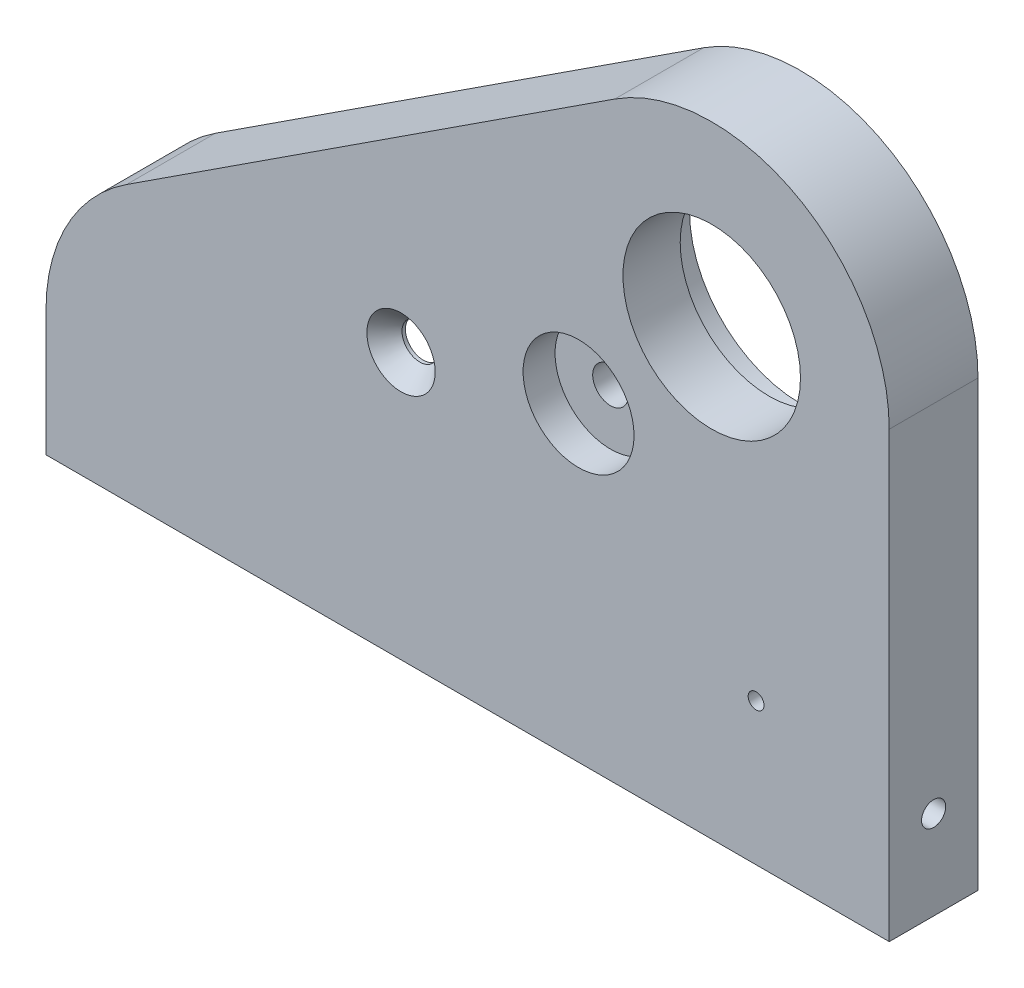
SolidWorks part; units mm, degrees
material "6061 Alloy"
ref_plane "Front Plane" through (0, 0, 0) normal (0, 0, 1) x (1, 0, 0)
ref_plane "Top Plane" through (0, 0, 0) normal (0, 1, 0) x (1, 0, 0)
ref_plane "Right Plane" through (0, 0, 0) normal (1, 0, 0) x (0, 0, -1)
sketch "Sketch1" plane through (0, 0, 0) normal (0, 0, 1) x (1, 0, 0)
  line L0 (25.4, 0) -> (25.4, -63.5)
  line L1 (25.4, -63.5) -> (-95.25, -63.5)
  line L2 (-95.25, -63.5) -> (-95.25, -31.75)
  line L3 (-13.8669, 21.2807) -> (-95.25, -31.75)
  arc A0 (25.4, 0) -> (-13.8669, 21.2807) centre (0, 0) ccw
  dimension "D1" = 50.8
  dimension "D2" = 63.5
  dimension "D4" = 31.75
  dimension "D5" = 120.65
extrude "Boss-Extrude1" add sketch "Sketch1" along normal mid plane 12.7
sketch "Sketch4" plane through (0, 0, 6.35) normal (0, 0, 1) x (1, 0, 0)
  circle A0 centre (0, 0) radius 12.7
  dimension "D1" = 25.4
extrude "Cut-Extrude3" cut sketch "Sketch4" against normal through all
sketch "Sketch5" plane through (0, 0, -6.35) normal (0, 0, -1) x (-1, 0, 0)
  circle A0 centre (0, 0) radius 15.875
  dimension "D1" = 31.75
extrude "Cut-Extrude4" cut sketch "Sketch5" against normal blind 4.5085
fillet "Fillet1" radius 25.4 1 edges at (-95.25, -31.75, 0)
hole_wizard "#8-32 Tapped Hole2" positions "Sketch17" profile "Sketch18" tap size "#8-32" standard "Ansi Inch"
sketch "Sketch17" plane through (25.4, 0, 0) normal (1, 0, 0) x (0, 0, -1)
  line L0 (-6.35, -63.5) -> (6.35, -63.5) construction
  point P0 (0, -50.8)
  dimension "D1" = 12.7
sketch "Sketch18" plane through (25.4, -50.8, 0) normal (0, 1, 0) x (0, 0, -1)
  line L0 (0, 0) -> (0, 11.7058)
  line L1 (0, 11.7058) -> (1.7272, 10.668)
  line L2 (1.7272, 10.668) -> (1.7272, 0)
  line L5 (1.7272, 0) -> (0, 0)
  line L10 (0, 11.7058) -> (-1.7272, 10.668) construction
  line L11 (0, -6.35) -> (0, 107.95) construction
  dimension "Tap Drill Dia." = 3.4544
  dimension "Tap Drill Depth" = 10.668
  dimension "Drill Angle" = 118
hole_wizard "1/4-20 Tapped Hole1" positions "Sketch24" profile "Sketch25" tap size "1/4-20" standard "Ansi Inch" end condition through all
sketch "Sketch24" plane through (0, 0, 6.35) normal (0, 0, 1) x (1, 0, 0)
  point P0 (-19.05, -19.05)
  dimension "D1" = 19.05
  dimension "D2" = 19.05
sketch "Sketch25" plane through (-19.05, -19.05, 6.35) normal (1, 0, 0) x (0, -1, 0)
  line L0 (0, 0) -> (0, 12.7)
  line L1 (0, 12.7) -> (2.5527, 12.7)
  line L2 (2.5527, 12.7) -> (2.5527, 0)
  line L5 (2.5527, 0) -> (0, 0)
  line L11 (0, -6.35) -> (0, 107.95) construction
  dimension "Thread Major Dia." = 5.1054
  dimension "Thru Tap Drill Depth" = 12.7
sketch "Sketch27" plane through (0, 0, 6.35) normal (0, 0, 1) x (1, 0, 0)
  circle A0 centre (-19.05, -19.05) radius 7.9375
  dimension "D1" = 15.875
extrude "Cut-Extrude6" cut sketch "Sketch27" against normal blind 4.572
sketch "Sketch28" plane through (0, 0, -6.35) normal (0, 0, -1) x (-1, 0, 0)
  line L0 (-19.05, -16.8005) -> (-19.05, -57.15)
  line L1 (-19.05, -57.15) -> (88.9, -57.15)
  line L2 (88.9, -57.15) -> (88.9, -45.5155)
  line L3 (80.2502, -29.555) -> (24.4761, 6.7884)
  line L4 (95.25, -63.5) -> (95.25, -45.5155)
  line L5 (83.7169, -24.2348) -> (13.8669, 21.2807)
  line L6 (-25.4, 0) -> (-25.4, -63.5)
  line L7 (-25.4, -63.5) -> (95.25, -63.5)
  line L8 (95.25, -63.5) -> (95.25, -45.5155) construction
  line L9 (83.7169, -24.2348) -> (13.8669, 21.2807) construction
  line L10 (-25.4, 0) -> (-25.4, -63.5) construction
  line L11 (-25.4, -63.5) -> (95.25, -63.5) construction
  circle A0 centre (0, 0) radius 25.4
  arc A1 (88.9, -45.5155) -> (80.2502, -29.555) centre (69.85, -45.5155) ccw
  arc A2 (95.25, -45.5155) -> (83.7169, -24.2348) centre (69.85, -45.5155) ccw
  arc A3 (13.8669, 21.2807) -> (-25.4, 0) centre (0, 0) ccw
  arc A4 (95.25, -45.5155) -> (83.7169, -24.2348) centre (69.85, -45.5155) ccw construction
  arc A5 (13.8669, 21.2807) -> (-25.4, 0) centre (0, 0) ccw construction
  circle A6 centre (19.05, -19.05) radius 9.525
  arc A7 (13.2298, -26.59) -> (5.3888, -24.8218) centre (7.4096, -34.1299) ccw
  arc A8 (28.5743, -19.1637) -> (48.2069, -8.675) centre (41.2734, -19.3154) cw
  dimension "D6" = 19.05
  dimension "D7" = 9.525
  dimension "D8" = 12.7
  dimension "D2" = 6.35
  dimension "D3" = 6.35
  dimension "D4" = 6.35
  dimension "D5" = 6.35
  dimension "D1" = 0
extrude "Cut-Extrude8" cut sketch "Sketch28" against normal offset from surface (9.525 mm away) 3.175 contours A8 A6 A7 A0 L0 L1 L2 A1 L3 region at (-34.7797, -38.1357, -6.35) up to face at (-11.1125, -19.05, 6.35)
fillet "Fillet2" radius 6.35 3 edges at (-88.9, -57.15, -1.5875) (19.05, -57.15, -1.5875) (19.05, -16.8005, -1.5875)
hole_wizard "#8-32 Tapped Hole1" positions "Sketch20" profile "Sketch21" tap size "#8-32" standard "Ansi Inch"
sketch "Sketch20" plane through (0, -63.5, 0) normal (0, -1, 0) x (1, 0, 0)
  line L0 (-82.55, 0) -> (12.7, 0) construction
  line L4 (-95.25, 6.35) -> (25.4, 6.35) construction
  line L6 (-34.925, 6.35) -> (-34.925, 0) construction
  point P0 (12.7, 0)
  point P7 (-34.925, 0)
  point P9 (-82.55, 0)
  dimension "D1" = 95.25
sketch "Sketch21" plane through (12.7, -63.5, 0) normal (1, 0, 0) x (0, 0, -1)
  line L0 (0, 0) -> (0, 11.7058)
  line L1 (0, 11.7058) -> (1.7272, 10.668)
  line L2 (1.7272, 10.668) -> (1.7272, 0)
  line L5 (1.7272, 0) -> (0, 0)
  line L10 (0, 11.7058) -> (-1.7272, 10.668) construction
  line L11 (0, -6.35) -> (0, 107.95) construction
  dimension "Tap Drill Dia." = 3.4544
  dimension "Tap Drill Depth" = 10.668
  dimension "Drill Angle" = 118
hole_wizard "#4-40 Tapped Hole1" positions "Sketch30" profile "Sketch31" tap size "#4-40" standard "Ansi Inch"
sketch "Sketch30" plane through (0, 0, 3.175) normal (0, 0, -1) x (-1, 0, 0)
  point P0 (-6.35, -43.18)
  dimension "D1" = 43.18
  dimension "D2" = 6.35
sketch "Sketch31" plane through (6.35, -43.18, 3.175) normal (1, 0, 0) x (0, 1, 0)
  line L0 (0, 0) -> (0, 8.2992)
  line L1 (0, 8.2992) -> (1.1303, 7.62)
  line L2 (1.1303, 7.62) -> (1.1303, 0)
  line L5 (1.1303, 0) -> (0, 0)
  line L10 (0, 8.2992) -> (-1.1303, 7.62) construction
  line L11 (0, -6.35) -> (0, 107.95) construction
  dimension "Tap Drill Dia." = 2.2606
  dimension "Tap Drill Depth" = 7.62
  dimension "Drill Angle" = 118
hole_wizard "CSK for #10 Flat Head Machine Screw1" positions "Sketch33" profile "Sketch32" countersink size "#10" standard "Ansi Inch" end condition through all
sketch "Sketch33" plane through (0, 0, 6.35) normal (0, 0, 1) x (1, 0, 0)
  line L0 (-95.25, -63.5) -> (25.4, -63.5) construction
  line L1 (-95.25, -45.5155) -> (-95.25, -63.5) construction
  point P0 (-44.45, -25.4)
  dimension "D1" = 38.1
  dimension "D2" = 50.8
sketch "Sketch32" plane through (-44.45, -25.4, 6.35) normal (1, 0, 0) x (0, -1, 0)
  line L0 (0, 0) -> (0, 12.7)
  line L1 (0, 12.7) -> (2.5527, 12.7)
  line L2 (2.5527, 12.7) -> (2.5527, 2.6882)
  line L3 (2.5527, 2.6882) -> (4.8895, 0)
  line L5 (4.8895, 0) -> (0, 0)
  line L6 (-2.5527, 2.6882) -> (-4.8895, 0) construction
  line L11 (0, -6.35) -> (0, 107.95) construction
  dimension "Thru Hole Dia." = 5.1054
  dimension "Thru Hole Depth" = 12.7
  dimension "Near C'Sink Dia." = 9.779
  dimension "Near C'Sink Angle" = 82
